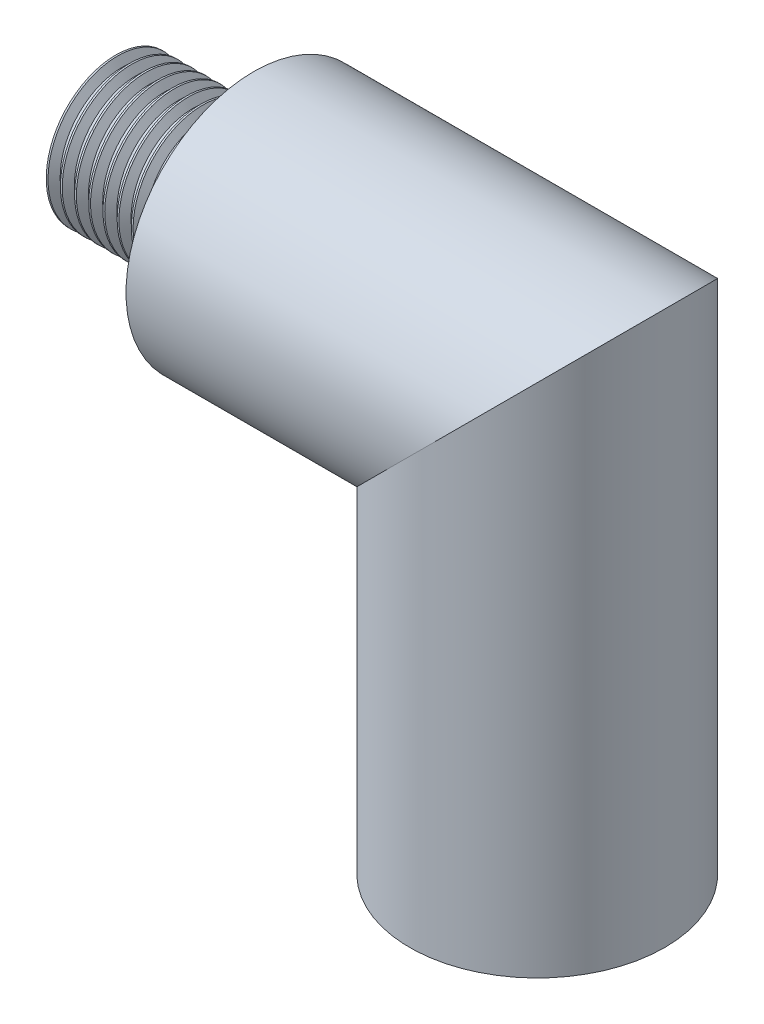
SolidWorks part; units mm, degrees
ref_plane "Front Plane" through (0, 0, 0) normal (0, 0, 1) x (1, 0, 0)
ref_plane "Top Plane" through (0, 0, 0) normal (0, 1, 0) x (1, 0, 0)
ref_plane "Right Plane" through (0, 0, 0) normal (1, 0, 0) x (0, 0, -1)
sketch "Sketch1" plane through (0, 0, 0) normal (0, 0, 1) x (1, 0, 0)
  line L0 (0, 0) -> (20, 0)
  line L1 (20, 0) -> (20, -30)
  dimension "D1" = 20
  dimension "D2" = 30
sweep "Sweep1" add path "Sketch1" circular profile diameter 18 parameters "D3"=18
sketch "Sketch13" plane through (0, 0, 0) normal (-1, 0, 0) x (0, 0, 1)
  circle A0 centre (0, 0) radius 5
  dimension "D1" = 10
extrude "Boss-Extrude1" add sketch "Sketch13" along normal blind 10
shell "Shell2" thickness 1 removed face at (-10, -5, 0)
thread "Thread1" pitch 1 method cut profile "Thread Profile1" start angle 0, offset 1, length 0, pitch 1, diameter 10
ref_plane "Plane1" through (-11, 0, -5) normal (0, -1, 0) x (0, 0, -1)
sketch "Thread Profile1" plane through (-11, 0, -5) normal (0, -1, 0) x (0, 0, -1)
  line L0 (0, 0) -> (0, 1) construction
  line L11 (0, 0) -> (0, 0.875)
  line L12 (0, 0.875) -> (-0.5413, 0.5625)
  line L13 (-0.5413, 0.5625) -> (-0.5413, 0.3125)
  line L15 (-0.5413, 0.3125) -> (0, 0)
  line L17 (-0.5413, 0.4375) -> (0, 0.4375) construction
  point P2 (0, 0)
  dimension "Pitch" = 1
  dimension "Profile_Angle" = 60
  dimension "Profile_Land" = 0.25
  dimension "Profile_Height" = 0.5413
sketch "Sketch20" plane through (0, -30, 0) normal (0, -1, 0) x (1, 0, 0)
  line L0 (0, 0) -> (20, 0) construction
  circle A0 centre (20, 0) radius 8
  dimension "D1" = 16
extrude "Cut-Extrude1" cut sketch "Sketch20" against normal up to next
